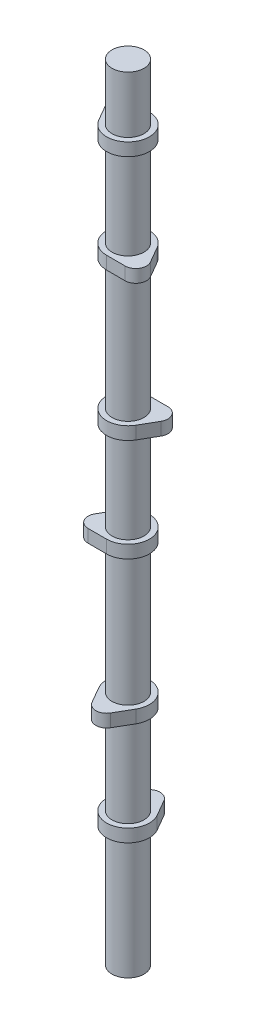
SolidWorks part; units mm, degrees
ref_plane "Front Plane" through (0, 0, 0) normal (0, 0, 1) x (1, 0, 0)
ref_plane "Top Plane" through (0, 0, 0) normal (0, 1, 0) x (1, 0, 0)
ref_plane "Right Plane" through (0, 0, 0) normal (1, 0, 0) x (0, 0, -1)
sketch "Sketch1" plane through (0, 0, 0) normal (0, 1, 0) x (1, 0, 0)
  line L0 (-5.4993, 15.875) -> (-10.9985, 6.35)
  line L1 (5.4993, 15.875) -> (10.9985, 6.35)
  arc A0 (-10.9985, 6.35) -> (10.9985, 6.35) centre (0, 0) ccw
  arc A1 (5.4993, 15.875) -> (-5.4993, 15.875) centre (0, 12.7) ccw
  point P9 (0, 0)
  dimension "D1" = 25.4
  dimension "D2" = 12.7
  dimension "D3" = 12.7
extrude "Boss-Extrude1" add sketch "Sketch1" along normal mid plane 7.62
ref_axis "Axis1" through (0, 176.0944, 0) along (0, -1, 0)
move or copy body "Body-Move/Copy1" bodies to move or copy 101 copy yes number of copies 1 translate (0, 60.96, 0)
move or copy body "Body-Move/Copy2" bodies to move or copy 102 copy no rotation origin (0, 0, 0) rotation axis (0, 1, 0) rotation angle 180
sketch "Sketch2" plane through (0, 0, 0) normal (0, 1, 0) x (1, 0, 0)
  circle A0 centre (0, 0) radius 9.5
  dimension "D1" = 19
extrude "Boss-Extrude2" add sketch "Sketch2" along normal mid plane 146.05 from offset 25.4
pattern_linear "LPattern1" count 3 spacing 146.05 along (0, 1, 0) of bodies 104
move or copy body "Body-Move/Copy3" bodies to move or copy 105 copy no rotation origin (0, 0, 0) rotation axis (0, 1, 0) rotation angle 120
move or copy body "Body-Move/Copy4" bodies to move or copy 106 copy no rotation origin (0, 0, 0) rotation axis (0, -1, 0) rotation angle 120
sketch "Sketch3" plane through (0, -47.625, 0) normal (0, -1, 0) x (1, 0, 0)
  circle A1 centre (0, 0) radius 9.5
  circle A2 centre (0, 0) radius 9.5
  dimension "D1" = 0
extrude "Boss-Extrude3" add sketch "Sketch3" along normal blind 27.94
combine bodies "Combine1" operation type add bodies to combine 109 107 108
